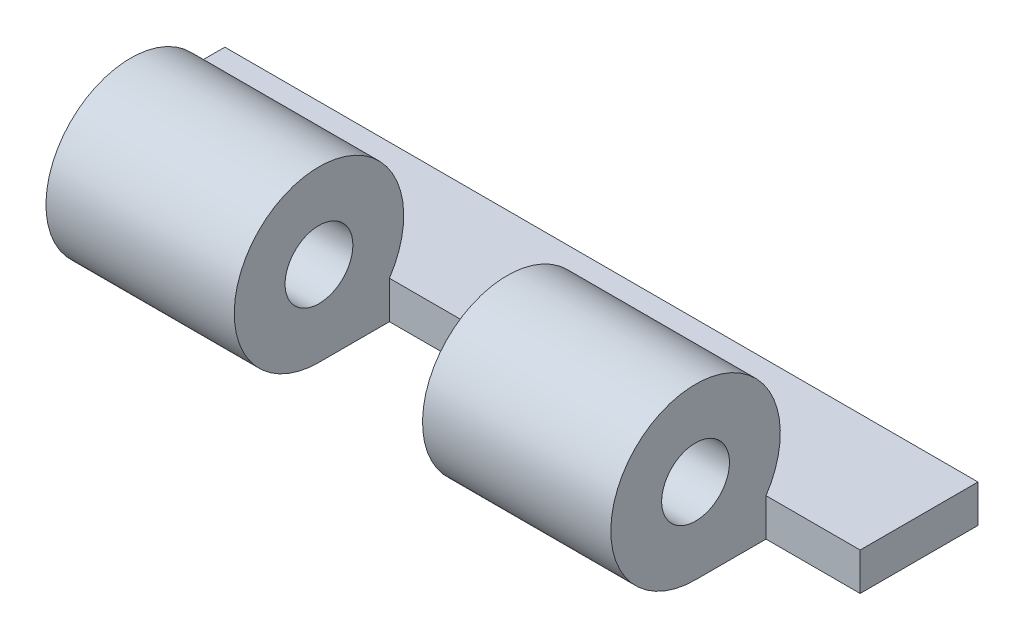
SolidWorks part; units mm, degrees
ref_plane "Ebene vorne" through (0, 0, 0) normal (0, 0, 1) x (1, 0, 0)
ref_plane "Ebene oben" through (0, 0, 0) normal (0, 1, 0) x (1, 0, 0)
ref_plane "Ebene rechts" through (0, 0, 0) normal (1, 0, 0) x (0, 0, -1)
sketch "Skizze2" plane through (0, 0, 0) normal (0, 1, 0) x (1, 0, 0)
  line L1 (-7.5, 2.5) -> (7.5, 2.5)
  line L2 (-7.5, 2.5) -> (-7.5, -2.5)
  line L3 (-7.5, -2.5) -> (7.5, -2.5)
  line L4 (7.5, 2.5) -> (7.5, -2.5)
  line L5 (-7.5, 2.5) -> (7.5, -2.5) construction
  line L6 (-7.5, -2.5) -> (7.5, 2.5) construction
  point P0 (0, 0)
  dimension "D1" = 15
  dimension "D2" = 5
extrude "Aufsatz-Linear austragen1" add sketch "Skizze2" along normal blind 1
sketch "Skizze3" plane through (7.5, 0, 0) normal (1, 0, 0) x (0, 0, -1)
  circle A0 centre (-2.5, 2.25) radius 2.25
  circle A1 centre (-2.5, 2.25) radius 0.9
  dimension "D1" = 1.8
  dimension "D2" = 4.5
extrude "Aufsatz-Linear austragen2" add sketch "Skizze3" against normal up to surface (15 mm away) up to face at (-7.5, 0.5, 0)
ref_plane "Tangential Ebene" through (0, 0, 0.25) normal (0, 0, -1) x (-1, 0, 0)
sketch "Skizze5" plane through (7.5, 0, 0) normal (1, 0, 0) x (0, 0, -1)
  line L0 (-0.6292, 1) -> (-0.6292, 0)
  line L1 (-0.6292, 0) -> (-2.5, 0)
  line L3 (2.5, 1) -> (-0.6292, 1)
  line L4 (-2.5, 0) -> (2.5, 0)
  line L5 (2.5, 0) -> (2.5, 1)
  line L6 (2.5, 1) -> (-0.6292, 1) construction
  line L7 (-2.5, 0) -> (2.5, 0) construction
  line L8 (2.5, 0) -> (2.5, 1) construction
  arc A1 (-0.6292, 1) -> (-2.5, 0) centre (-2.5, 2.25) ccw
  arc A2 (-0.6292, 1) -> (-2.5, 0) centre (-2.5, 2.25) ccw
  dimension "D1" = 0
extrude "Schnitt-Linear austragen1" cut sketch "Skizze5" against normal blind 5 from offset 5 offset against normal yes
ref_plane "Spiegelebene" through (0, 0, 0) normal (1, 0, 0) x (0, 0, -1)
sketch "Skizze7" plane through (7.5, 0, 0) normal (1, 0, 0) x (0, 0, -1)
  line L1 (-0.6292, 1) -> (2.5, 1)
  line L2 (-0.6292, 1) -> (-0.6292, 0)
  line L3 (-0.6292, 0) -> (2.5, 0)
  line L4 (2.5, 1) -> (2.5, 0)
extrude "Aufsatz-Linear austragen3" add sketch "Skizze7" along normal blind 2.5
mirror "Spiegeln1" about plane through (0, 0, 0) normal (1, 0, 0) of "Aufsatz-Linear austragen3"
